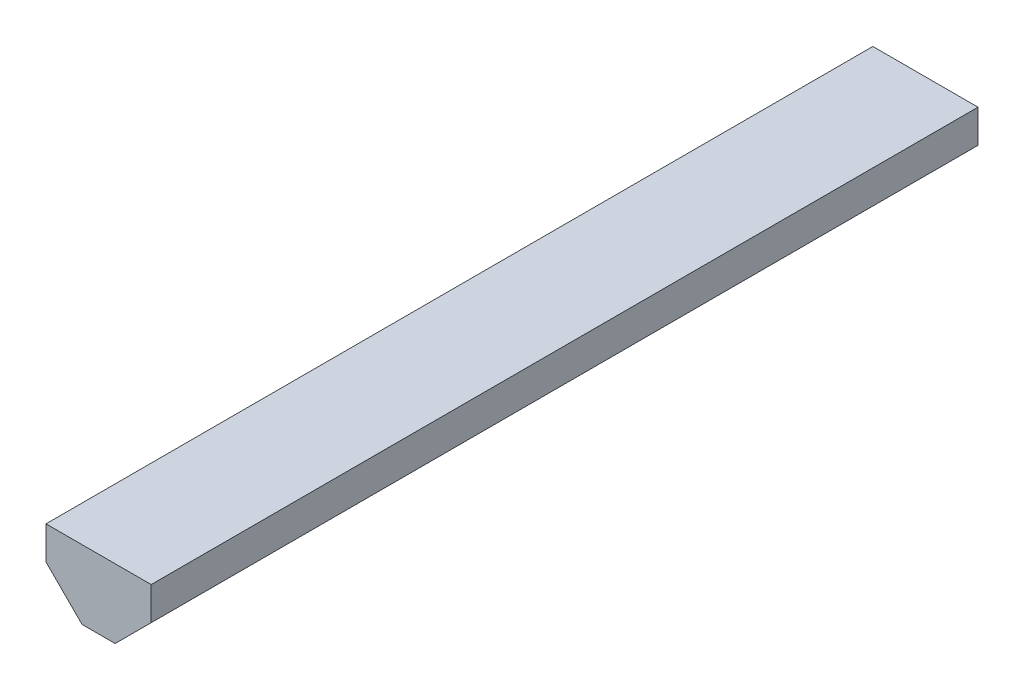
SolidWorks part; units mm, degrees
ref_plane "Front Plane" through (0, 0, 0) normal (0, 0, 1) x (1, 0, 0)
ref_plane "Top Plane" through (0, 0, 0) normal (0, 1, 0) x (1, 0, 0)
ref_plane "Right Plane" through (0, 0, 0) normal (1, 0, 0) x (0, 0, -1)
sketch "Sketch1" plane through (0, 0, 0) normal (0, 0, 1) x (1, 0, 0)
  line L0 (19.05, -60.5751) -> (-19.05, -60.5751)
  line L1 (-19.05, -60.5751) -> (-60.5751, -19.05)
  line L2 (19.05, -60.5751) -> (60.5751, -19.05)
  line L3 (-60.5751, -19.05) -> (-60.5751, 19.05)
  line L4 (-60.5751, 19.05) -> (60.5751, 19.05)
  line L5 (60.5751, 19.05) -> (60.5751, -19.05)
  circle A0 centre (0, 0) radius 63.5 construction
  dimension "D1" = 127
  dimension "D2" = 45
  dimension "D3" = 45
  dimension "D4" = 38.1
extrude "Boss-Extrude1" add sketch "Sketch1" along normal blind 952.5
equation "\"fuse_diam\"= 10"
equation "\"fuse_rad\"= 5.0"
equation "\"fuse_length\"= 25"
equation "\"wing_rotation_hor\"= 6.25"
equation "\"wing_rotation_vert\"= 3.0"
equation "\"tail_length\"= 37.5"
equation "\"tail_diam\"= 5.0"
equation "\"tail_rad\"= 2.5"
equation "\"tail_connector\"= 12.375"
equation "\"wingspan\"= 100"
equation "\"wing_mount_diam\"= 3"
equation "\"tail_elevation\"= 1.0"
equation "\"tail_chord_length\"= 3"
equation "\"nose_cone_length\"= 12.5"
equation "\"nose_cone_splinex\"= 9.5"
equation "\"nose_cone_spliney\"= 2.4"
equation "\"wing_chord_length\"= 5"
equation "\"tri_length\"= 1.5"
equation "\"tri_degrees\"= 45"
equation "\"tail_connect_top\"= 2.25"
equation "\"tail_connect_bottom\"= 2.384848003542364"
equation "\"D1@Sketch1\"=\"tail_diam\""
equation "\"D2@Sketch1\"=\"tri_degrees\""
equation "\"D3@Sketch1\"=\"tri_degrees\""
equation "\"D4@Sketch1\"=\"tri_length\""
equation "\"D1@Boss-Extrude1\"=\"tail_length\""
